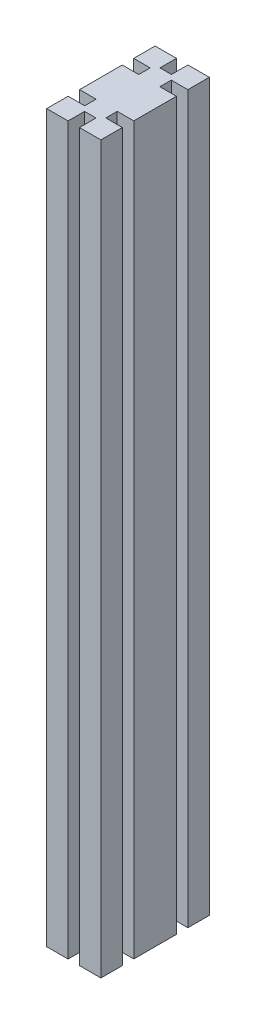
SolidWorks part; units mm, degrees
ref_plane "Front Plane" through (0, 0, 0) normal (0, 0, 1) x (1, 0, 0)
ref_plane "Top Plane" through (0, 0, 0) normal (0, 1, 0) x (1, 0, 0)
ref_plane "Right Plane" through (0, 0, 0) normal (1, 0, 0) x (0, 0, -1)
sketch "Sketch1" plane through (0, 0, 0) normal (0, 1, 0) x (1, 0, 0)
  line L0 (0, 0) -> (-18.9548, 0) construction
  line L1 (-18.9548, -37.9412) -> (18.9548, -37.9412)
  line L2 (-18.9548, -37.9412) -> (-18.9548, 37.9412)
  line L3 (-18.9548, 37.9412) -> (18.9548, 37.9412)
  line L4 (18.9548, -37.9412) -> (18.9548, 37.9412)
  line L5 (-18.9548, -37.9412) -> (18.9548, 37.9412) construction
  line L6 (-18.9548, 37.9412) -> (18.9548, -37.9412) construction
  line L7 (0, 0) -> (0, -37.9412) construction
  line L8 (-7.3977, 22.9362) -> (-7.3977, 14.9225)
  line L9 (-18.9548, -22.9362) -> (-7.3977, -22.9362)
  line L10 (-18.9548, -22.9362) -> (-18.9548, -14.9225)
  line L11 (-18.9548, -14.9225) -> (-7.3977, -14.9225)
  line L12 (-7.3977, -22.9362) -> (-7.3977, -14.9225)
  line L13 (4.0068, -26.3842) -> (-4.0069, -26.3842)
  line L14 (4.0068, -26.3842) -> (4.0069, -37.9412)
  line L15 (4.0069, -37.9412) -> (-4.0069, -37.9412)
  line L16 (-4.0069, -26.3842) -> (-4.0069, -37.9412)
  line L17 (4.0068, -26.3842) -> (-4.0069, -37.9412) construction
  line L18 (4.0069, -37.9412) -> (-4.0069, -26.3842) construction
  line L19 (-18.9548, 14.9225) -> (-7.3977, 14.9225)
  line L20 (-18.9547, 22.9362) -> (-18.9548, 14.9225)
  line L21 (-18.9547, 22.9362) -> (-7.3977, 22.9362)
  line L22 (4.0069, 37.9412) -> (-4.0068, 26.3842) construction
  line L23 (4.0069, 26.3842) -> (-4.0068, 37.9412) construction
  line L24 (-4.0068, 26.3842) -> (-4.0068, 37.9412)
  line L25 (4.0069, 37.9412) -> (-4.0068, 37.9412)
  line L26 (4.0069, 26.3842) -> (4.0069, 37.9412)
  line L27 (4.0069, 26.3842) -> (-4.0068, 26.3842)
  line L28 (18.9548, 22.9362) -> (7.3978, 22.9362)
  line L29 (18.9548, 22.9362) -> (18.9548, 14.9225)
  line L30 (18.9548, 14.9225) -> (7.3978, 14.9225)
  line L31 (7.3978, 22.9362) -> (7.3978, 14.9225)
  line L32 (7.3978, -22.9362) -> (7.3978, -14.9225)
  line L33 (18.9548, -14.9225) -> (7.3978, -14.9225)
  line L34 (18.9548, -22.9362) -> (18.9548, -14.9225)
  line L35 (18.9548, -22.9362) -> (7.3978, -22.9362)
  line L36 (-7.3977, 18.9293) -> (-64.053, 18.9293) construction
  line L37 (-64.053, 18.9293) -> (-64.053, -18.9294) construction
  line L38 (-64.053, -18.9294) -> (-7.3977, -18.9294) construction
  point P0 (0, 0)
  point P13 (0, -32.1627)
  point P26 (0, 32.1627)
  dimension "D1" = 37.9095
  dimension "D2" = 75.8825
  dimension "D3" = 29.845
  dimension "D4" = 8.0137
  dimension "D5" = 11.557
  dimension "D6" = 37.8587
extrude "Boss-Extrude1" add sketch "Sketch1" along normal blind 508 contours L4 L35 L32 L33 L30 L31 L28 L3 L26 L27 L24 L2 L21 L8 L19 L11 L12 L9 L1 L16 L13 L14 region at (0, 0, 0)
